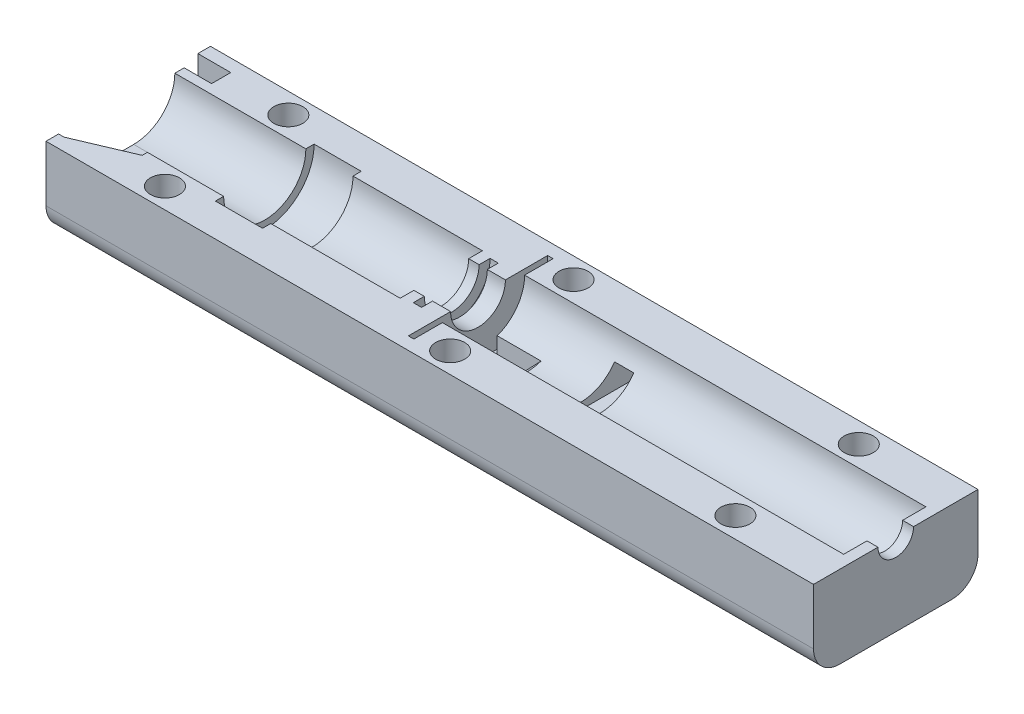
SolidWorks part; units mm, degrees
ref_plane "Front Plane" through (0, 0, 0) normal (0, 0, 1) x (1, 0, 0)
ref_plane "Top Plane" through (0, 0, 0) normal (0, 1, 0) x (1, 0, 0)
ref_plane "Right Plane" through (0, 0, 0) normal (1, 0, 0) x (0, 0, -1)
sketch "Sketch2" plane through (0, 0, 0) normal (0, 1, 0) x (1, 0, 0)
  line L0 (0, -15) -> (140, -15)
  line L1 (0, 0) -> (140, 0)
  line L2 (0, -15) -> (0, 15)
  line L3 (0, 15) -> (140, 15)
  line L4 (140, -15) -> (140, 15)
  dimension "D1" = 140
  dimension "D2" = 15
extrude "Base" add sketch "Sketch2" against normal blind 15 contours L0 L4 L1 L2 | L1 L4 L3 L2
sketch "Sketch3" plane through (0, 0, 0) normal (-1, 0, 0) x (0, 0, 1)
  circle A0 centre (0, 0) radius 7.5
  dimension "D1" = 15
extrude "Center_cut" cut sketch "Sketch3" against normal through all
sketch "Sketch4" plane through (0, 0, 0) normal (0, 1, 0) x (1, 0, 0)
  line L0 (0, 15) -> (140, 15) construction
  line L1 (0, 12.7) -> (1, 12.7)
  line L2 (0, 12.7) -> (0, -12.7)
  line L3 (0, -12.7) -> (1, -12.7)
  line L4 (1, 12.7) -> (1, -12.7)
  line L5 (0, 7.5) -> (0, 15) construction
  dimension "D1" = 25.4
  dimension "D2" = 2.3
  dimension "D3" = 0
  dimension "D4" = 1
extrude "Antenna_PCB" cut sketch "Sketch4" against normal blind 10.2
sketch "Sketch11" plane through (1, 0, 0) normal (-1, 0, 0) x (0, 0, 1)
  line L0 (-7.5, 0) -> (-12.7, 0) construction
  line L1 (-12.7, 7.5) -> (-9.2, 7.5)
  line L2 (-12.7, 7.5) -> (-12.7, -7.5)
  line L3 (-12.7, -7.5) -> (-9.2, -7.5)
  line L4 (-9.2, 7.5) -> (-9.2, -7.5)
  line L5 (-12.7, 7.5) -> (-9.2, -7.5) construction
  line L6 (-12.7, -7.5) -> (-9.2, 7.5) construction
  line L7 (-12.7, -10.2) -> (-12.7, 0) construction
  point P0 (-10.95, 0)
  dimension "D1" = 3.5
  dimension "D2" = 0
  dimension "D3" = 15
extrude "Coax_connector" cut sketch "Sketch11" against normal blind 5
sketch "Sketch8" plane through (1, 0, 0) normal (-1, 0, 0) x (0, 0, 1)
  circle A0 centre (0, 0) radius 9
  dimension "D1" = 18
extrude "Lens" cut sketch "Sketch8" against normal blind 8.6 from offset 23.9 offset against normal yes
fillet "Fillet1" radius 4.8 2 edges at (70, -15, 15) (70, -15, -15)
sketch "Sketch17" plane through (0, 0, -15) normal (0, 0, -1) x (-1, 0, 0)
  line L0 (-140, -10.2) -> (0, -10.2) construction
  line L1 (-86, -10.2) -> (-3.5, -10.2)
  line L2 (-86, -10.2) -> (-86, -7.2)
  line L3 (-86, -7.2) -> (-3.5, -7.2)
  line L4 (-3.5, -10.2) -> (-3.5, -7.2)
  line L5 (0, -10.2) -> (0, 0) construction
  dimension "D1" = 3.5
  dimension "D2" = 86
  dimension "D3" = 3
extrude "Cut-Extrude4" cut sketch "Sketch17" against normal blind 2
sketch "Sketch19" plane through (0, 0, -15) normal (0, 0, -1) x (-1, 0, 0)
  line L5 (0, 0) -> (-140, 0) construction
  line L6 (-3.5, -10.2) -> (-7.5, -10.2)
  line L7 (-3.5, -10.2) -> (-3.5, -5)
  line L8 (-3.5, -5) -> (-7.5, -5)
  line L9 (-7.5, -10.2) -> (-7.5, -5)
  dimension "D1" = 4
  dimension "D2" = 5
extrude "Cut-Extrude5" cut sketch "Sketch19" against normal blind 5.8
sketch "Sketch21" plane through (0, 0, -15) normal (0, 0, -1) x (-1, 0, 0)
  line L0 (-86, -7.2) -> (-86, -10.2) construction
  line L5 (-86, -8.7) -> (-82.5, -8.7)
  line L6 (-86, -8.7) -> (-86, -4.2)
  line L7 (-86, -4.2) -> (-82.5, -4.2)
  line L8 (-82.5, -8.7) -> (-82.5, -4.2)
  dimension "D1" = 4.5
  dimension "D2" = 3.5
extrude "Cut-Extrude6" cut sketch "Sketch21" against normal blind 15
fillet "Fillet7" radius 1.5 1 edges at (84.25, -8.7, -13)
sketch "Sketch22" plane through (140, 0, 0) normal (1, 0, 0) x (0, 0, -1)
  line L0 (-11.25, 0) -> (-11.25, -14.8837) construction
  line L1 (-15, 0) -> (-7.5, 0) construction
  line L2 (7.5, 0) -> (15, 0) construction
  line L3 (11.25, 0) -> (-11.25, 0)
  line L4 (11.25, 0) -> (11.25, -8)
  line L5 (11.25, -8) -> (-11.25, -8)
  line L6 (-11.25, 0) -> (-11.25, -8)
  arc A0 (-15, -10.2) -> (-10.2, -15) centre (-10.2, -10.2) ccw construction
  arc A1 (3.25, 0) -> (-3.25, 0) centre (0, 0) cw
  line M7 (15, 0) -> (7.5, 0)
  arc M8 (7.5, 0) -> (-7.5, 0) centre (0, 0) cw
  line M9 (-7.5, 0) -> (-15, 0)
  dimension "D2" = 3.25
  dimension "D1" = 8
extrude "Coax_cable_hole" add sketch "Sketch22" against normal blind 2 contours L3 A1 M8 | L6 L5 L4 M9 M7 M8
sketch "Sketch23" plane through (1, 0, 0) normal (-1, 0, 0) x (0, 0, 1)
  line L8 (0, -7.5) -> (12.7, -7.5)
  line L9 (0, -7.5) -> (0, 0)
  line L10 (0, 0) -> (12.7, 0)
  line L11 (12.7, -7.5) -> (12.7, 0)
  arc A1 (-7.5, 0) -> (7.5, 0) centre (0, 0) ccw construction
extrude "Cut-Extrude7" cut sketch "Sketch23" against normal blind 10
sketch "Sketch24" plane through (0, 0, 0) normal (0, 1, 0) x (1, 0, 0)
  line L5 (1, -12.7) -> (11, -8.4553)
  line L6 (11, -12.7) -> (11, -7.5) construction
  line L7 (0, -12.7) -> (11, -12.7) construction
  line L8 (11, -8.4553) -> (11, -12.7)
  line L9 (11, -12.7) -> (1, -12.7)
  dimension "D1" = 23
extrude "Boss-Extrude1" add sketch "Sketch24" against normal up to next
sketch "Sketch27" plane through (0, -7.5, 0) normal (0, 1, 0) x (1, 0, 0)
  line L0 (11, -8.4553) -> (10.6874, -7.7188)
  line L1 (11, -8.4553) -> (1, -12.7) construction
  line L2 (1, -12.7) -> (0.6874, -11.9636)
  line L3 (10.6874, -7.7188) -> (0.6874, -11.9636)
  line L4 (10.6874, -7.7188) -> (11, -7.5862)
  line L5 (11, 0) -> (11, -8.4553) construction
  line L6 (11, -7.5862) -> (11, -8.4553)
  line L7 (1, -12.7) -> (1, -11.8309)
  line L8 (1, 0) -> (1, -12.7) construction
  line M3 (1, 0) -> (1, -12.7)
  line M4 (1, -12.7) -> (11, -8.4553)
  line M5 (11, -8.4553) -> (11, 0)
  dimension "D1" = 90
  dimension "D2" = 90
  dimension "D3" = 0.8
  dimension "D4" = 0.8
extrude "Cut-Extrude10" cut sketch "Sketch27" against normal blind 2.7 contours L4 L0 M5 | L0 L3 M3 M4
sketch "Sketch31" plane through (0, 0, 0) normal (0, 1, 0) x (1, 0, 0)
  line L0 (17.95, -7.5) -> (17.95, -15) construction
  line L1 (11, -7.5) -> (24.9, -7.5) construction
  line L2 (0, -15) -> (140, -15) construction
  line L3 (17.95, -11.25) -> (122, -11.25) construction
  line L4 (122, -7.5) -> (122, -15) construction
  line L5 (33.5, -7.5) -> (138, -7.5) construction
  line L6 (140, -15) -> (140, -3.25) construction
  line L7 (11, 0) -> (1, 0) construction
  circle A0 centre (17.95, -11.25) radius 2.65
  circle A1 centre (122, -11.25) radius 2.65
  circle A2 centre (122, 11.25) radius 2.65
  circle A3 centre (17.95, 11.25) radius 2.65
  circle A4 centre (69.975, -11.25) radius 2.65
  circle A5 centre (69.975, 11.25) radius 2.65
  dimension "D2" = 5.3
  dimension "D3" = 5.3
  dimension "D4" = 5.3
  dimension "D1" = 18
extrude "Mounting_holes" cut sketch "Sketch31" against normal blind 5
fillet "Fillet11" radius 2 2 edges at (7.5, -8.7, -13) (3.5, -7.5, -10.95) profile chamfer
sketch "Sketch10" plane through (1, 0, 0) normal (-1, 0, 0) x (0, 0, 1)
  line L1 (12.7, 10.2) -> (-12.7, 10.2)
  line L2 (12.7, 10.2) -> (12.7, -10.2)
  line L3 (12.7, -10.2) -> (-12.7, -10.2)
  line L4 (-12.7, 10.2) -> (-12.7, -10.2)
  line L5 (12.7, 10.2) -> (-12.7, -10.2) construction
  line L6 (12.7, -10.2) -> (-12.7, 10.2) construction
  point P0 (0, 0)
extrude "Photodiode_PCB" cut sketch "Sketch10" against normal blind 1 from offset 62.8 offset against normal yes
sketch "Sketch33" plane through (64.8, 0, 0) normal (-1, 0, 0) x (0, 0, 1)
  line L0 (-12.7, -10.2) -> (12.7, -10.2) construction
  line L1 (2.5, -10.2) -> (-2.5, -10.2)
  line L2 (0, -10.2) -> (0, -5.7)
  line L3 (2.5, -5.7) -> (-2.5, -5.7)
  line L4 (-2.5, -10.2) -> (-2.5, -5.7)
  line L5 (2.5, -10.2) -> (2.5, -5.7)
  line M7 (-12.7, -10.2) -> (12.7, -10.2)
  arc M10 (7.5, 0) -> (-7.5, 0) centre (0, 0) cw
  dimension "D1" = 4.5
  dimension "D2" = 2.5
extrude "Cut-Extrude13" cut sketch "Sketch33" against normal blind 5 contours L4 L2 M7 M10 | L1 L5 L2 M10
chamfer "Chamfer2" distance 3 angle 45 1 edges at (69.8, -7.5, 0)
sketch "Sketch35" plane through (1, 0, 0) normal (-1, 0, 0) x (0, 0, 1)
  line L0 (-7.5, 0) -> (-3.25, 0) construction
  line L1 (3.25, 0) -> (7.5, 0) construction
  line L2 (-7.5, 0) -> (-5, 0)
  line L3 (5, 0) -> (7.5, 0)
  circle A0 centre (0, 0) radius 7.5
  arc A1 (-5, 0) -> (5, 0) centre (0, 0) ccw
  arc M4 (0, -7.5) -> (-7.5, 0) centre (0, 0) cw
  dimension "D1" = 5
extrude "Filter_mount" add sketch "Sketch35" against normal blind 6.7 from offset 56.1 contours A1 L2 A0 L3 M4 offset against normal yes
sketch "Sketch36" plane through (1, 0, 0) normal (-1, 0, 0) x (0, 0, 1)
  circle A0 centre (0, 0) radius 7
  dimension "D1" = 14
extrude "Filter_space" cut sketch "Sketch36" against normal blind 1.5 from offset 58
